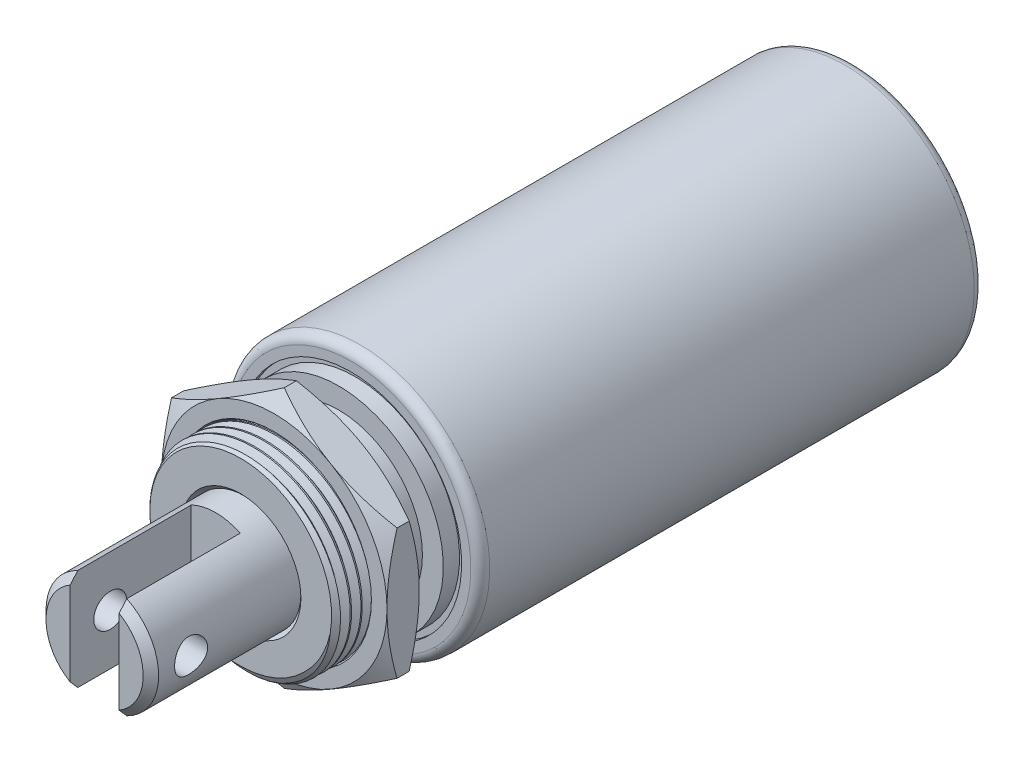
SolidWorks part; units mm, degrees
ref_plane "Front Plane" through (0, 0, 0) normal (0, 0, 1) x (1, 0, 0)
ref_plane "Top Plane" through (0, 0, 0) normal (0, 1, 0) x (1, 0, 0)
ref_plane "Right Plane" through (0, 0, 0) normal (1, 0, 0) x (0, 0, -1)
sketch "Sketch0" plane through (0, 0, 0) normal (1, 0, 0) x (0, 0, -1)
  line L0 (0, 0) -> (51.1556, 0) construction
  line L1 (0, 0) -> (-24.0538, 0) construction
  line L2 (51.1556, 12.7635) -> (51.1556, -12.7635) construction
  line L3 (0, 9.464) -> (0, -9.464) construction
  line L4 (-24.0538, 5.5499) -> (-24.0538, -5.5499) construction
  line L5 (-24.0538, 0) -> (-49.4538, 0) construction
  point P10 (-20.0914, 0)
  point P12 (-9.652, 0)
  dimension "D1" = 20.0914
  dimension "Lg." = 51.1556
  dimension "Dia." = 25.527
  dimension "Rod Dia." = 11.0998
  dimension "A" = 24.0538
  dimension "Thread OD" = 18.9281
  dimension "Stroke" = 25.4
  dimension "D2" = 3.9624
  dimension "D3" = 9.652
sketch "Sketch1" plane through (0, 0, 0) normal (1, 0, 0) x (0, 0, -1)
  line L0 (51.1556, 0) -> (0, 0) construction
  line L1 (49.8729, 12.7635) -> (2.1209, 12.7635)
  line L2 (51.1556, 2.2225) -> (51.1556, 0)
  line L3 (51.1556, 0) -> (0, 0)
  line L4 (1.6002, 10.922) -> (1.6002, 10.3124)
  line L5 (50.8, 2.5781) -> (50.8, 11.8364)
  line L6 (1.1938, 11.8364) -> (1.1938, 10.922)
  line L7 (1.1938, 10.922) -> (1.6002, 10.922)
  line L8 (1.6002, 10.3124) -> (0, 10.3124)
  line L9 (0, 10.3124) -> (0, 0)
  arc A0 (51.1556, 2.2225) -> (50.8, 2.5781) centre (50.8, 2.2225) ccw
  arc A1 (50.8, 11.8364) -> (49.8729, 12.7635) centre (49.8729, 11.8364) ccw
  arc A2 (1.1938, 11.8364) -> (2.1209, 12.7635) centre (2.1209, 11.8364) cw
  dimension "D1" = 0.9271
  dimension "D4" = 1.1938
  dimension "D2" = 0.3556
  dimension "D3" = 4.445
  dimension "D5" = 21.844
  dimension "D6" = 0.4064
  dimension "D7" = 20.6248
revolve "Revolve1" add sketch "Sketch1" angle 360 mid plane about L0
sketch "Sketch2" plane through (0, 0, 0) normal (1, 0, 0) x (0, 0, -1)
  line L0 (0, 0) -> (-24.0538, 0) construction
  line L3 (-9.652, 5.9309) -> (-9.652, 8.956)
  line L4 (-9.652, 8.956) -> (-9.144, 9.464)
  line L5 (-9.144, 9.464) -> (-2.479, 9.464)
  line L6 (-2.479, 9.464) -> (-1.27, 8.255)
  line L7 (-1.27, 8.255) -> (0, 8.255)
  line L8 (0, 8.255) -> (0, 5.5499)
  line L9 (-9.271, 5.5499) -> (0, 5.5499)
  line L11 (-9.271, 5.5499) -> (-9.652, 5.9309)
  dimension "D1" = 1.27
  dimension "D4" = 0.508
  dimension "D5" = 9.652
  dimension "D2" = 45
  dimension "D6" = 1.209
  dimension "D3" = 45
  dimension "D8" = 0.381
  dimension "D7" = 45
revolve "Revolve2" add sketch "Sketch2" angle 360 mid plane about L0
sketch "Sketch3" plane through (0, 0, 0) normal (1, 0, 0) x (0, 0, -1)
  line L0 (-24.0538, 0) -> (0, 0) construction
  line L1 (-23.2918, 5.5499) -> (-24.0538, 4.7879)
  line L2 (0, 0) -> (-24.0538, 0)
  line L3 (0, 0) -> (0, 5.5499)
  line L4 (0, 5.5499) -> (-23.2918, 5.5499)
  line L5 (-24.0538, 0) -> (-24.0538, 4.7879)
  line L6 (-23.2918, 5.5499) -> (-24.0538, 5.5499) construction
  line L7 (-24.0538, 5.5499) -> (-24.0538, 4.7879) construction
  dimension "D1" = 0.762
revolve "Revolve3" add sketch "Sketch3" angle 360 mid plane about L2
sketch "Sketch4" plane through (0, 0, 0) normal (0, 1, 0) x (0, 0, -1)
  line L1 (-24.0538, 2.413) -> (-12.1158, 2.413)
  line L2 (-24.0538, 2.413) -> (-24.0538, -2.413)
  line L3 (-24.0538, -2.413) -> (-12.1158, -2.413)
  line L4 (-12.1158, 2.413) -> (-12.1158, -2.413)
  dimension "D1" = 4.826
  dimension "D2" = 11.938
extrude "Cut-Extrude1" cut sketch "Sketch4" against normal up to surface and the other way up to surface up to face at (0, 5.5499, 23.2918) other way up to face at (0, 5.5499, 23.2918)
sketch "Sketch5" plane through (0, 0, 0) normal (1, 0, 0) x (0, -1, 0)
  line L0 (0, -24.0538) -> (0, -20.0914) construction
  circle A0 centre (0, -20.0914) radius 1.6256
  dimension "D1" = 3.2512
extrude "Cut-Extrude2" cut sketch "Sketch5" along normal up to surface and the other way up to surface up to face at (0, 0, 17.7038) other way up to face at (0, 0, 17.7038)
sketch "Sketch6" plane through (0, 0, 9.652) normal (0, 0, 1) x (1, 0, 0)
  circle A1 centre (0, 0) radius 9.464
  point P1 (0, 9.464)
curve "Helix/Spiral1" pitch 1.0583 height 9.4403 radius 9.464 centre (0, 0, 9.652) axis (0, 0, -1) start towards (0, 1, 0) parameters "Pitch"=1.0583
sketch "Sketch7" plane through (0, 0, 0) normal (1, 0, 0) x (0, 0, -1)
  line L0 (-10.6442, 9.5786) -> (-9.5859, 9.5786) construction
  line L1 (-9.5859, 9.5786) -> (-10.115, 8.6621) construction
  line L2 (-10.115, 8.6621) -> (-10.6442, 9.5786) construction
  line L3 (-10.1812, 8.7766) -> (-10.0489, 8.7766) construction
  line L4 (-10.578, 9.464) -> (-9.652, 9.464) construction
  line L5 (-10.115, 8.6621) -> (-10.115, 8.7766) construction
  line L6 (-10.115, 9.464) -> (-10.115, 9.5786) construction
  line L7 (-10.1812, 8.7766) -> (-10.0489, 8.7766)
  line L8 (-10.0489, 8.7766) -> (-9.6189, 9.5213)
  line L9 (-9.6189, 9.5213) -> (-10.6111, 9.5213)
  line L10 (-10.6111, 9.5213) -> (-10.1812, 8.7766)
  line L11 (-10.115, 8.6621) -> (-10.115, -9.464) construction
  line L12 (-10.115, -9.464) -> (-9.0567, -9.464) construction
  line L13 (-9.0567, -9.464) -> (-7.9984, -9.464) construction
  line L14 (-7.9984, -9.464) -> (-6.94, -9.464) construction
  line L15 (-9.144, -9.464) -> (-2.479, -9.464) construction
  point P15 (-10.115, 9.5213)
  dimension "D1" = 1.0583
  dimension "D2" = 0.1323
sweep "Cut-Sweep1" cut profiles "Sketch7" path "Helix/Spiral1" align with end faces yes
move or copy body "Body-Move/Copy1" bodies to move or copy 107 copy yes number of copies 1 translate (0, 0, 25.4)
sketch "SketchX" plane through (0, 0, 0) normal (1, 0, 0) x (0, 0, -1)
  line L0 (-48.6918, -4.9979) -> (-37.5158, -4.9979) construction
  line L2 (-48.6918, 4.9979) -> (-37.5158, 4.9979) construction
  line L3 (-49.4538, 4.1354) -> (-49.4538, -4.1354) construction
  line L4 (-49.4538, 4.1354) -> (-49.4538, -4.1354)
  line L7 (-37.5158, 5.5499) -> (-37.5158, 4.9979) construction
  line L8 (-25.4, 5.5499) -> (-37.5158, 5.5499) construction
  line L11 (-37.5158, -4.9979) -> (-37.5158, -5.5499) construction
  line L12 (-37.5158, -5.5499) -> (-25.4, -5.5499) construction
  line L13 (-48.6918, -4.9979) -> (-37.5158, -4.9979)
  line L15 (-48.6918, 4.9979) -> (-37.5158, 4.9979)
  line L16 (-37.5158, 5.5499) -> (-37.5158, 4.9979)
  line L17 (-12.1158, 5.5499) -> (-37.5158, 5.5499)
  line L18 (-37.5158, -4.9979) -> (-37.5158, -5.5499)
  line L19 (-37.5158, -5.5499) -> (-12.1158, -5.5499)
  circle A2 centre (-45.4914, 0) radius 1.6256 construction
  circle A5 centre (-45.4914, 0) radius 1.6256
  spline S0 degree 3 poles (-1434.4786, -1445.2829) (1443.8208, 1319.7519) (-1538.9887, -1332.4105) (1339.788, 1433.0653) knots -101.772608 -101.772608 -101.772608 -101.772608 98.765964 98.765964 98.765964 98.765964 only from (-48.6918, -4.9979) to (-49.4538, -4.1354) construction
  spline S1 degree 3 poles (1394.5661, -1377.9374) (-1596.4208, 1274.6807) (1503.9715, -1259.3485) (-1497.3844, 1382.1644) knots -97.820644 -97.820644 -97.820644 -97.820644 102.837817 102.837817 102.837817 102.837817 only from (-49.4538, 4.1354) to (-48.6918, 4.9979) construction
  spline S2 degree 3 poles (-48.6918, -4.9979) (-48.9485, -4.7129) (-49.203, -4.4258) (-49.4538, -4.1354) knots 0 0 0 0 1 1 1 1
  spline S3 degree 3 poles (-49.4538, 4.1354) (-49.203, 4.4258) (-48.9485, 4.7129) (-48.6918, 4.9979) knots 0 0 0 0 1 1 1 1
delete or keep bodies "Body-Delete1" type delete bodies bodies 108
sketch "Sketch8" plane through (0, 0, -50.8) normal (0, 0, -1) x (-1, 0, 0)
  line L0 (-10.16, -2.54) -> (-10.16, 2.54) construction
  line L1 (0, 0) -> (-10.16, 0) construction
  circle A0 centre (-10.16, 2.54) radius 0.381
  circle A1 centre (-10.16, -2.54) radius 0.381
  dimension "D1" = 0.762
  dimension "D2" = 5.08
  dimension "D3" = 10.16
extrude "Boss-Extrude1" [suppressed] add sketch "Sketch8" along normal blind 152.4
sketch "Sketch9" plane through (0, 0, -50.8) normal (0, 0, -1) x (-1, 0, 0)
  circle A0 centre (-10.16, 2.54) radius 0.7874
  circle A1 centre (-10.16, -2.54) radius 0.7874
  circle A3 centre (-10.16, -2.54) radius 0.381
  circle A4 centre (-10.16, -2.54) radius 0.381
  circle A5 centre (-10.16, 2.54) radius 0.381
  circle A6 centre (-10.16, 2.54) radius 0.381
  dimension "D3" = 1.5748
  dimension "D1" = 0
  dimension "D2" = 0
extrude "Boss-Extrude2" [suppressed] add sketch "Sketch9" along normal blind 139.7
sketch "Sketch10" plane through (0, 0, 0) normal (0, 0, 1) x (1, 0, 0)
  line L0 (0, 9.464) -> (0, 11.1125) construction
  line L1 (0, 12.8316) -> (-11.1125, 6.4158)
  line L2 (-11.1125, 6.4158) -> (-11.1125, -6.4158)
  line L3 (-11.1125, -6.4158) -> (0, -12.8316)
  line L4 (0, -12.8316) -> (11.1125, -6.4158)
  line L5 (11.1125, -6.4158) -> (11.1125, 6.4158)
  line L6 (11.1125, 6.4158) -> (0, 12.8316)
  circle A0 centre (0, 0) radius 9.464
  circle A1 centre (0, 0) radius 11.1125 construction
  dimension "D1" = 22.225
extrude "Boss-Extrude3" add sketch "Sketch10" along normal blind 3.175 from offset 3.175 separate body
sketch "Sketch11" plane through (0, 0, 0) normal (1, 0, 0) x (0, 0, -1)
  line L0 (-6.35, 0) -> (-3.175, 0) construction
  line L1 (-6.35, 12.8316) -> (-6.35, 11.1125)
  line L2 (-6.35, 6.4158) -> (-6.35, 12.8316) construction
  line L3 (-6.35, 11.1125) -> (-5.3575, 12.8316)
  line L4 (-6.35, 12.8316) -> (-3.175, 12.8316) construction
  line L5 (-5.3575, 12.8316) -> (-6.35, 12.8316)
  line L6 (-3.175, 12.8316) -> (-3.175, 11.1125)
  line L7 (-3.175, 6.4158) -> (-3.175, 12.8316) construction
  line L8 (-3.175, 11.1125) -> (-4.1675, 12.8316)
  line L9 (-4.1675, 12.8316) -> (-3.175, 12.8316)
  line L10 (-6.35, 11.1125) -> (0, 11.1125) construction
  line L11 (-6.35, 9.5786) -> (-6.35, 9.464)
  line L12 (-6.35, 9.464) -> (-6.2354, 9.464)
  line L13 (-6.2354, 9.464) -> (-6.35, 9.5786)
  line L14 (-3.175, 9.5786) -> (-3.175, 9.464)
  line L15 (-3.175, 9.464) -> (-3.2896, 9.464)
  line L16 (-3.2896, 9.464) -> (-3.175, 9.5786)
  line L18 (-6.35, 9.5786) -> (-10.115, 9.5786) construction
  line L20 (-6.35, 9.464) -> (-6.35, -9.464) construction
  line L21 (-3.175, -9.464) -> (-3.175, 9.464) construction
  dimension "D1" = 30
revolve "Cut-Revolve1" cut sketch "Sketch11" angle 360 about L0
equation "\"D3@Helix/Spiral1\" = \"Pitch@Helix/Spiral1\" + \"D5@Sketch2\" - \"D1@Sketch2\""
equation "\"D1@Sketch7\" = \"Pitch@Helix/Spiral1\""
equation "\"D2@Sketch7\" = \"D1@Sketch7\" / 8"
